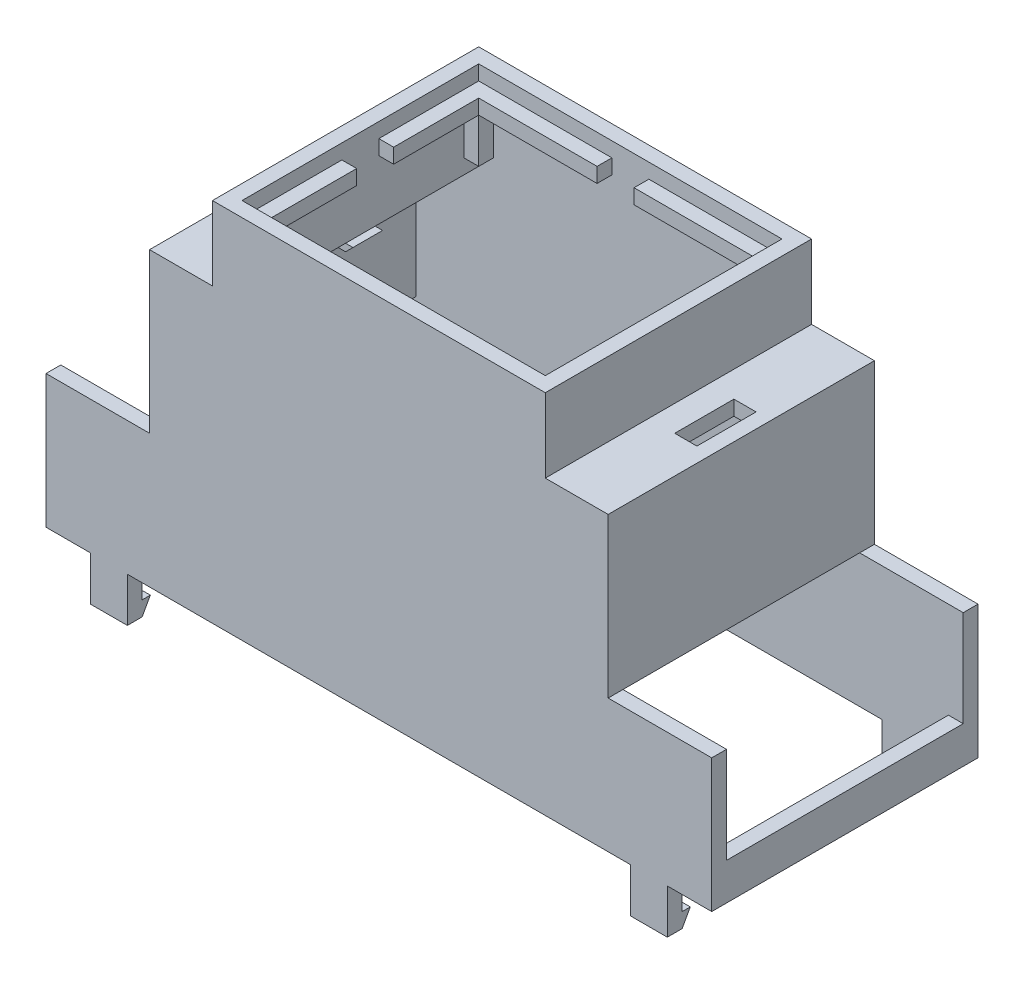
SolidWorks part; units mm, degrees
ref_plane "Спереди" through (0, 0, 0) normal (0, 0, 1) x (1, 0, 0)
ref_plane "Сверху" through (0, 0, 0) normal (0, 1, 0) x (1, 0, 0)
ref_plane "Справа" through (0, 0, 0) normal (1, 0, 0) x (0, 0, -1)
sketch "Эскиз1" plane through (0, 0, 0) normal (0, 1, 0) x (1, 0, 0)
  line L1 (45, -18) -> (-45, -18)
  line L2 (45, -18) -> (45, 18)
  line L3 (45, 18) -> (-45, 18)
  line L4 (-45, -18) -> (-45, 18)
  line L5 (45, -18) -> (-45, 18) construction
  line L6 (45, 18) -> (-45, -18) construction
  point P0 (0, 0)
  dimension "D1" = 90
  dimension "D2" = 36
extrude "Вытянуть-Тонкостенный1" add sketch "Эскиз1" along normal blind 18 thin thin type one direction reverse wall 2
sketch "Эскиз2" plane through (0, 18, 0) normal (0, 1, 0) x (1, 0, 0)
  line L0 (45, 18) -> (-45, 18) construction
  line L1 (31, -18) -> (-31, -18)
  line L2 (31, -18) -> (31, 18)
  line L3 (31, 18) -> (-31, 18)
  line L4 (-31, -18) -> (-31, 18)
  line L5 (31, -18) -> (-31, 18) construction
  line L6 (31, 18) -> (-31, -18) construction
  point P0 (0, 0)
  dimension "D1" = 62
extrude "Вытянуть-Тонкостенный2" add sketch "Эскиз2" along normal blind 21.5 thin thin type one direction reverse wall 2
sketch "Эскиз3" plane through (0, 39.5, 0) normal (0, 1, 0) x (1, 0, 0)
  line L0 (31, 18) -> (-31, 18) construction
  line L1 (22.5, -18) -> (-22.5, -18)
  line L2 (22.5, -18) -> (22.5, 18)
  line L3 (22.5, 18) -> (-22.5, 18)
  line L4 (-22.5, -18) -> (-22.5, 18)
  line L5 (22.5, -18) -> (-22.5, 18) construction
  line L6 (22.5, 18) -> (-22.5, -18) construction
  point P0 (0, 0)
  dimension "D1" = 45
extrude "Вытянуть-Тонкостенный3" add sketch "Эскиз3" along normal blind 10 thin thin type one direction reverse wall 2
sketch "Эскиз4" plane through (0, 39.5, 0) normal (0, 1, 0) x (1, 0, 0)
  line L0 (-22.5, -18) -> (22.5, -18) construction
  line L1 (-31, 18) -> (-20.5, 18)
  line L2 (-31, 18) -> (-31, -18)
  line L3 (-31, -18) -> (-20.5, -18)
  line L4 (-20.5, 18) -> (-20.5, -18)
  line L6 (31, 18) -> (20.5, 18)
  line L7 (31, 18) -> (31, -18)
  line L8 (31, -18) -> (20.5, -18)
  line L9 (20.5, 18) -> (20.5, -18)
  line L11 (20.5, -16) -> (20.5, 16) construction
  line L12 (-20.5, 16) -> (-20.5, -16) construction
extrude "Бобышка-Вытянуть1" add sketch "Эскиз4" against normal blind 2
sketch "Эскиз5" plane through (-45, 0, 0) normal (-1, 0, 0) x (0, 0, 1)
  line L0 (-18, 18) -> (18, 18) construction
  line L1 (16, 18) -> (-16, 18)
  line L2 (16, 18) -> (16, 5)
  line L3 (16, 5) -> (-16, 5)
  line L4 (-16, 18) -> (-16, 5)
  line L5 (-16, 5) -> (-18, 5) construction
  line L6 (-18, 18) -> (-18, 0) construction
  line L7 (16, 5) -> (18, 5) construction
  line L8 (18, 18) -> (18, 0) construction
  dimension "D1" = 2
  dimension "D2" = 13
extrude "Вырез-Вытянуть1" cut sketch "Эскиз5" against normal up to surface (90 mm away) up to face at (45, 9, 0)
sketch "Эскиз6" plane through (0, 0, 0) normal (0, -1, 0) x (1, 0, 0)
  line L0 (-45, 18) -> (-39, 18) construction
  line L1 (-45, 18) -> (45, 18) construction
  line L2 (-43, 16) -> (43, 16) construction
  line L3 (-39, 18) -> (-34, 18)
  line L4 (-39, 18) -> (-39, 16)
  line L5 (-39, 16) -> (-34, 16)
  line L6 (-34, 18) -> (-34, 16)
  line L7 (0, 0) -> (0, 18) construction
  line L8 (0, 0) -> (-45, 0) construction
  line L9 (-45, -18) -> (-45, 18) construction
  line L10 (-34, -18) -> (-34, -16)
  line L11 (-39, -16) -> (-34, -16)
  line L12 (-39, -18) -> (-39, -16)
  line L13 (-39, -18) -> (-34, -18)
  line L14 (39, -18) -> (34, -18)
  line L15 (39, -18) -> (39, -16)
  line L16 (39, -16) -> (34, -16)
  line L17 (34, -18) -> (34, -16)
  line L18 (34, 18) -> (34, 16)
  line L19 (39, 16) -> (34, 16)
  line L20 (39, 18) -> (39, 16)
  line L21 (39, 18) -> (34, 18)
  dimension "D1" = 6
  dimension "D2" = 5
extrude "Бобышка-Вытянуть2" add sketch "Эскиз6" along normal blind 6
sketch "Эскиз7" plane through (-39, 0, 0) normal (-1, 0, 0) x (0, 0, 1)
  line L0 (-16, -6) -> (-14.9, -4)
  line L1 (-14.9, -4) -> (-16, -4)
  line L2 (-16, -6) -> (-16, 0) construction
  line M5 (-16, -6) -> (-16, 0)
  dimension "D1" = 1.1
  dimension "D2" = 2
extrude "Бобышка-Вытянуть3" add sketch "Эскиз7" against normal blind 5 contours L0 L1 M5 region at (-39, -4.6667, -15.6333)
mirror "Зеркальное отражение1" about plane through (0, 0, 0) normal (1, 0, 0) of "Бобышка-Вытянуть3"
mirror "Зеркальное отражение2" about plane through (0, 0, 0) normal (0, 0, 1) of "Бобышка-Вытянуть3", "Зеркальное отражение1"
sketch "Эскиз8" plane through (0, 49.5, 0) normal (0, 1, 0) x (1, 0, 0)
  line L0 (-18.5, -2.5) -> (-18.5, 2.5)
  line L1 (-20.5, 16) -> (20.5, 16)
  line L2 (-20.5, 16) -> (-20.5, -16)
  line L3 (-20.5, -16) -> (20.5, -16)
  line L4 (20.5, 16) -> (20.5, -16)
  line L5 (18.5, -14) -> (-18.5, -14)
  line L6 (18.5, -14) -> (18.5, 14)
  line L7 (18.5, 14) -> (-18.5, 14)
  line L8 (-18.5, -14) -> (-18.5, 14)
  line L9 (18.5, -14) -> (-18.5, 14) construction
  line L10 (18.5, 14) -> (-18.5, -14) construction
  line L11 (-18.5, 2.5) -> (-20.5, 2.5)
  line L12 (-20.5, -2.5) -> (-18.5, -2.5)
  line L13 (0, 0) -> (0, 14) construction
  line L14 (0, 0) -> (18.5, 0) construction
  line L15 (2.5, 14) -> (-2.5, 14)
  line L16 (-2.5, 14) -> (-2.5, 16)
  line L17 (2.5, 14) -> (2.5, 16)
  line L18 (20.5, -2.5) -> (18.5, -2.5)
  line L19 (18.5, 2.5) -> (20.5, 2.5)
  line L20 (2.5, -14) -> (2.5, -16)
  line L21 (-2.5, -14) -> (-2.5, -16)
  point P6 (0, 0)
  point P15 (-18.5, 0)
  point P23 (0, 14)
  line M12 (20.5, -16) -> (-20.5, -16)
  line M13 (-20.5, -16) -> (-20.5, 16)
  line M14 (-20.5, 16) -> (20.5, 16)
  line M15 (20.5, 16) -> (20.5, -16)
  dimension "D1" = 2
  dimension "D2" = 2
  dimension "D3" = 5
  dimension "D4" = 5
extrude "Бобышка-Вытянуть4" add sketch "Эскиз8" against normal blind 2 from offset 2 contours L7 L16 L2 L11 L8 M14 | L21 L5 L8 L12 M13 M12 | L5 L20 L4 L18 L6 M12 | L6 L19 L17 L7 M15 M14 region at (-18.725, 49.5, 8.25) region at (-19.5, 49.5, -2.725) region at (10.5, 49.5, 14.225) region at (2.725, 49.5, -15) offset against normal yes
sketch "Эскиз9" plane through (-20.5, 0, 0) normal (1, 0, 0) x (0, 0, -1)
  line L0 (0, 37.5) -> (0, 49.5) construction
  line L1 (-16, 45.5) -> (-14, 45.5)
  line L2 (-16, 45.5) -> (-16, 39.5)
  line L3 (-16, 39.5) -> (-14, 39.5)
  line L4 (-14, 45.5) -> (-14, 39.5)
  line L5 (16, 37.5) -> (-16, 37.5) construction
  line L6 (16, 49.5) -> (-16, 49.5) construction
  line L7 (16, 45.5) -> (14, 45.5)
  line L8 (16, 45.5) -> (16, 39.5)
  line L9 (14, 45.5) -> (14, 39.5)
  line L10 (16, 39.5) -> (14, 39.5)
  dimension "D1" = 2
  dimension "D2" = 2
extrude "Бобышка-Вытянуть5" add sketch "Эскиз9" along normal blind 2
mirror "Зеркальное отражение3" about plane through (0, 0, 0) normal (1, 0, 0) of "Бобышка-Вытянуть5"
sketch "Эскиз10" plane through (0, 0, -18) normal (0, 0, -1) x (-1, 0, 0)
  line L0 (20.5, 37.5) -> (19.5, 37.5)
  line L1 (19.5, 37.5) -> (20.5, 36.5)
  line L2 (20.5, 36.5) -> (22.5, 36.5)
  line L3 (22.5, 36.5) -> (22.5, 37.5)
  line L4 (20.5, 37.5) -> (29, 37.5) construction
  line L5 (20.5, 36.5) -> (20.5, 37.5) construction
  line L44 (-18.5, 39.5) -> (-20.5, 39.5)
  line L45 (-18.5, 45.5) -> (-18.5, 39.5)
  line L46 (-2.5, 45.5) -> (-18.5, 45.5)
  line L47 (-2.5, 47.5) -> (-2.5, 45.5)
  line L48 (-20.5, 47.5) -> (-2.5, 47.5)
  line L49 (-20.5, 49.5) -> (-20.5, 47.5)
  line L50 (20.5, 49.5) -> (-20.5, 49.5)
  line L51 (20.5, 47.5) -> (20.5, 49.5)
  line L52 (2.5, 47.5) -> (20.5, 47.5)
  line L53 (2.5, 45.5) -> (2.5, 47.5)
  line L54 (18.5, 45.5) -> (2.5, 45.5)
  line L55 (18.5, 39.5) -> (18.5, 45.5)
  line L56 (20.5, 39.5) -> (18.5, 39.5)
  line L57 (20.5, 37.5) -> (20.5, 39.5)
  line L58 (29, 37.5) -> (20.5, 37.5)
  line L59 (29, 18) -> (29, 37.5)
  line L60 (31, 18) -> (29, 18)
  line L61 (45, 18) -> (31, 18)
  line L62 (45, 5) -> (45, 18)
  line L63 (43, 5) -> (45, 5)
  line L64 (43, 0) -> (43, 5)
  line L65 (39, 0) -> (43, 0)
  line L66 (39, -4) -> (39, 0)
  line L67 (34, -4) -> (39, -4)
  line L68 (34, 0) -> (34, -4)
  line L69 (-34, 0) -> (34, 0)
  line L70 (-34, -4) -> (-34, 0)
  line L71 (-39, -4) -> (-34, -4)
  line L72 (-39, 0) -> (-39, -4)
  line L73 (-43, 0) -> (-39, 0)
  line L74 (-43, 5) -> (-43, 0)
  line L75 (-45, 5) -> (-43, 5)
  line L76 (-45, 18) -> (-45, 5)
  line L77 (-31, 18) -> (-45, 18)
  line L78 (-29, 18) -> (-31, 18)
  line L79 (-29, 37.5) -> (-29, 18)
  line L80 (-20.5, 37.5) -> (-29, 37.5)
  line L81 (-20.5, 39.5) -> (-20.5, 37.5)
  line L96 (22.5, 37.5) -> (20.5, 37.5)
  dimension "D1" = 1
  dimension "D2" = 1
  dimension "D3" = 2
  dimension "D4" = 0
extrude "Бобышка-Вытянуть6" add sketch "Эскиз10" along normal mid plane 4 from offset 18 contours L5 L2 L3 L96 | L1 L5 L0 region at (-20.1667, 37.1667, -18) region at (-21.5, 37, -18) offset against normal yes
mirror "Зеркальное отражение4" about plane through (0, 0, 0) normal (1, 0, 0) of "Бобышка-Вытянуть6"
sketch "Эскиз11" plane through (0, 0, -16) normal (0, 0, -1) x (-1, 0, 0)
  line L0 (0, 49.5) -> (0, 0) construction
  line L1 (29, 37.5) -> (27, 37.5)
  line L2 (29, 37.5) -> (29, 32.5)
  line L3 (29, 32.5) -> (27, 32.5)
  line L4 (27, 37.5) -> (27, 32.5)
  line L5 (-20.5, 49.5) -> (20.5, 49.5) construction
  line L6 (-27, 37.5) -> (-27, 32.5)
  line L7 (-29, 32.5) -> (-27, 32.5)
  line L8 (-29, 37.5) -> (-29, 32.5)
  line L9 (-29, 37.5) -> (-27, 37.5)
  line L10 (29, 30.5) -> (-29, 30.5) construction
  line L11 (29, 37.5) -> (29, 18) construction
  line L12 (-29, 37.5) -> (-29, 18) construction
  line L13 (-2.5, 30.5) -> (2.5, 30.5)
  line L14 (2.5, 30.5) -> (2.5, 22.5)
  line L15 (2.5, 22.5) -> (-2.5, 22.5)
  line L16 (-2.5, 22.5) -> (-2.5, 30.5)
  point P20 (0, 30.5)
  point P24 (0, 30.5)
  line M61 (20.5, 37.5) -> (29, 37.5)
  line M62 (29, 37.5) -> (29, 18)
  line M82 (-29, 18) -> (-29, 37.5)
  line M83 (-29, 37.5) -> (-20.5, 37.5)
  dimension "D1" = 2
  dimension "D2" = 5
  dimension "D3" = 2
  dimension "D4" = 5
  dimension "D5" = 8
extrude "Бобышка-Вытянуть7" add sketch "Эскиз11" against normal blind 4 contours L4 L3 M61 M62 | L7 L6 M82 M83 region at (-28, 35, -16) region at (28, 35, -16)
mirror "Зеркальное отражение5" about plane through (0, 0, 0) normal (0, 0, 1) of "Бобышка-Вытянуть7"
sketch "Эскиз12" plane through (29, 0, 0) normal (-1, 0, 0) x (0, 0, 1)
  line L0 (-12, 32.5) -> (12, 32.5) construction
  line L1 (12, 32.5) -> (0, 32.5) construction
  line L2 (0, 32.5) -> (0, 30.5) construction
  line L4 (-2.5, 30.5) -> (2.5, 30.5)
  line L5 (-2.5, 30.5) -> (-2.5, 24.5)
  line L6 (-2.5, 24.5) -> (2.5, 24.5)
  line L7 (2.5, 30.5) -> (2.5, 24.5)
  point P11 (0, 30.5)
  dimension "D1" = 2
  dimension "D2" = 6
  dimension "D3" = 5
extrude "Бобышка-Вытянуть8" add sketch "Эскиз12" along normal blind 1
sketch "Эскиз13" plane through (0, 0, -2.5) normal (0, 0, -1) x (-1, 0, 0)
  line L0 (-29, 24.5) -> (-28, 30.5)
  line L1 (-28, 30.5) -> (-28, 24.5)
  line L2 (-28, 24.5) -> (-29, 24.5)
  line L3 (-29, 24.5) -> (-28.9969, 24.5171)
  line M2 (-29, 24.5) -> (-28, 24.5)
  line M3 (-28, 24.5) -> (-28, 30.5)
extrude "Вырез-Вытянуть2" cut sketch "Эскиз13" against normal up to next contours L0 M2 M3 region at (28.3333, 26.5, -2.5)
mirror "Зеркальное отражение6" about plane through (0, 0, 0) normal (1, 0, 0) of "Вырез-Вытянуть2", "Бобышка-Вытянуть8"
sketch "Эскиз14" plane through (0, 39.5, 0) normal (0, 1, 0) x (1, 0, 0)
  line L0 (-29, 0) -> (-31, 0) construction
  line L1 (-26, 4) -> (-29, 4)
  line L2 (-26, 4) -> (-26, -4)
  line L3 (-26, -4) -> (-29, -4)
  line L4 (-29, 4) -> (-29, -4)
  line L5 (-31, 18) -> (-31, -18) construction
  dimension "D1" = 8
  dimension "D2" = 2
  dimension "D3" = 3
extrude "Вырез-Вытянуть3" cut sketch "Эскиз14" against normal up to next
mirror "Зеркальное отражение7" about plane through (0, 0, 0) normal (1, 0, 0) of "Вырез-Вытянуть3"
equation "\"width\"=36"
equation "\"D2@Эскиз1\"=\"width\""
